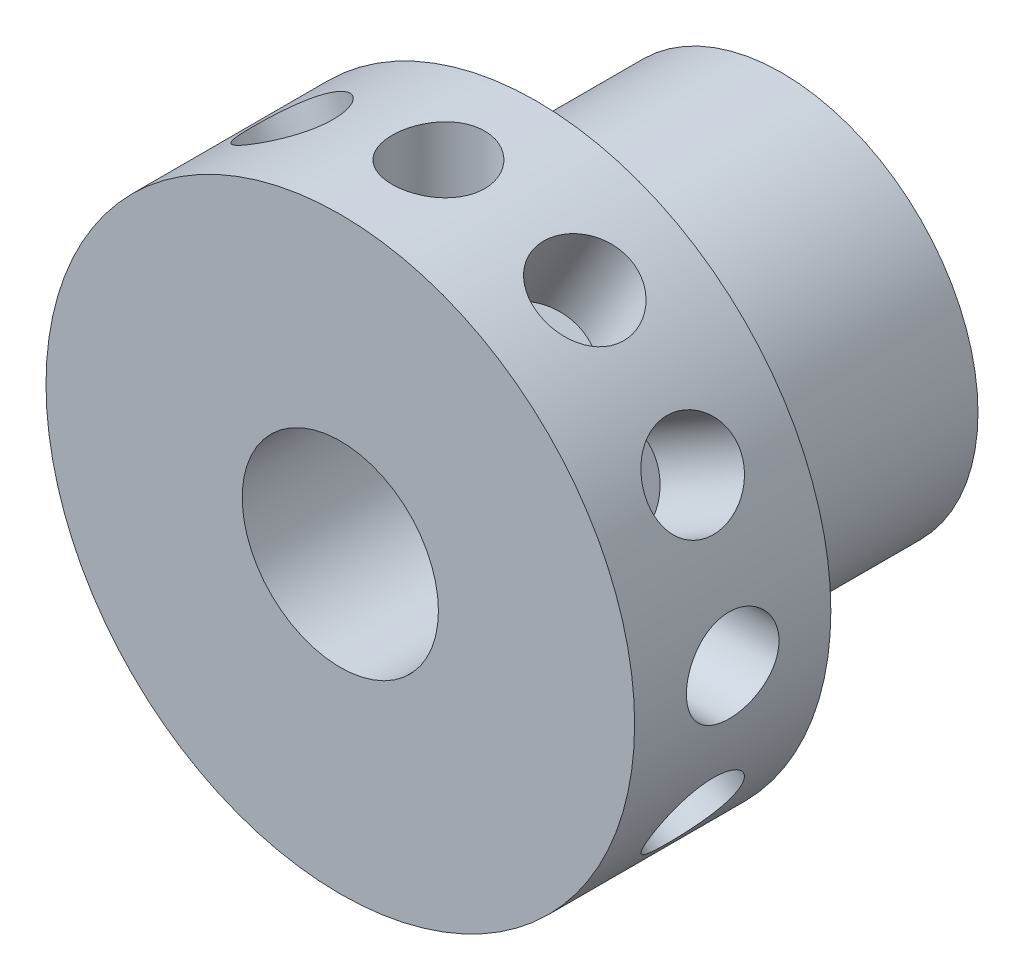
SolidWorks part; units mm, degrees
material "ABS"
ref_plane "Front Plane" through (0, 0, 0) normal (0, 0, 1) x (1, 0, 0)
ref_plane "Top Plane" through (0, 0, 0) normal (0, 1, 0) x (1, 0, 0)
ref_plane "Right Plane" through (0, 0, 0) normal (1, 0, 0) x (0, 0, -1)
ref_axis "X" through (-88.99, 0, 0) along (1, 0, 0)
ref_axis "Y" through (0, 55, 0) along (0, -1, 0)
ref_axis "Z" through (0, 0, -88.99) along (0, 0, 1)
sketch "Sketch1" plane through (0, 0, 0) normal (0, 0, 1) x (1, 0, 0)
  circle A0 centre (0, 0) radius 2
  circle A1 centre (0, 0) radius 6
  circle A2 centre (0, 0) radius 4
  dimension "D1" = 4
  dimension "D3" = 8
  dimension "D2" = 4
extrude "Boss-Extrude1" add sketch "Sketch1" along normal mid plane 4 contours A1 A2 | A2 A0 region at (-5.8303, 0, 0) region at (-3.8869, 0, 0)
ref_plane "Plane1" through (0, -6, 0) normal (0, -1, 0) x (-1, 0, 0)
sketch "Sketch3" plane through (0, -6, 0) normal (0, -1, 0) x (-1, 0, 0)
  circle A0 centre (0, 0) radius 0.9438
  circle A1 centre (0, 0) radius 0.7937 construction
  dimension "D1" = 0.15
extrude "Cut-Extrude1" cut sketch "Sketch3" against normal blind 2
pattern_circular "CirPattern1" count 12 over 360 about axis through (0, 0, -88.99) along (0, 0, 1) of "Cut-Extrude1"
extrude "Boss-Extrude2" add sketch "Sketch1<3>" against normal blind 5 from surface contours A2 A0 region at (-3.8869, 0, 0) starting at face at (6, 0, -2)
sketch "Sketch1<3>" plane through (0, 0, 0) normal (0, 0, 1) x (1, 0, 0) same geometry as "Sketch1"
equation "\"Axle Diameter\"= 0.4cm"
equation "\"D1@Sketch1\"=\"Axle Diameter\""
